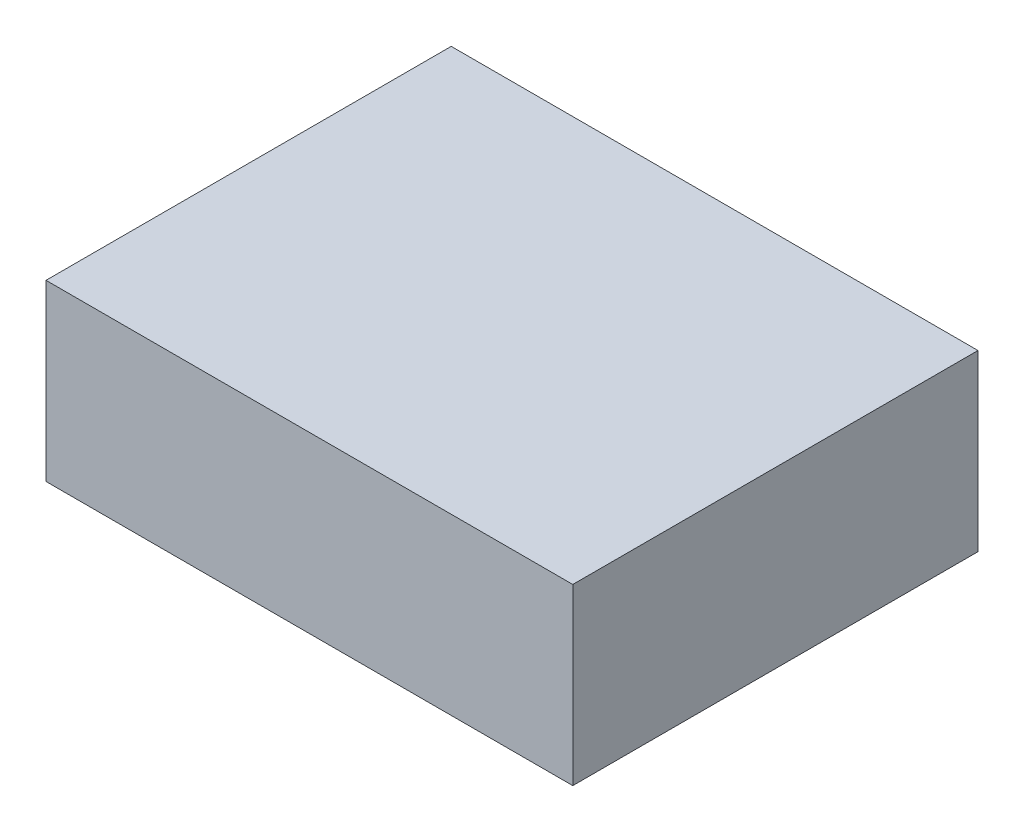
SolidWorks part; units mm, degrees
material "Liga 1060"
ref_plane "Plano frontal" through (0, 0, 0) normal (0, 0, 1) x (1, 0, 0)
ref_plane "Plano superior" through (0, 0, 0) normal (0, 1, 0) x (1, 0, 0)
ref_plane "Plano direito" through (0, 0, 0) normal (1, 0, 0) x (0, 0, -1)
sketch "Esboço1" plane through (0, 0, 0) normal (0, 1, 0) x (1, 0, 0)
  line L1 (-65, 50) -> (65, 50)
  line L2 (-65, 50) -> (-65, -50)
  line L3 (-65, -50) -> (65, -50)
  line L4 (65, 50) -> (65, -50)
  line L5 (-65, 50) -> (65, -50) construction
  line L6 (-65, -50) -> (65, 50) construction
  point P0 (0, 0)
  dimension "D1" = 130
  dimension "D2" = 100
extrude "Ressalto-extrusão1" add sketch "Esboço1" along normal blind 43
